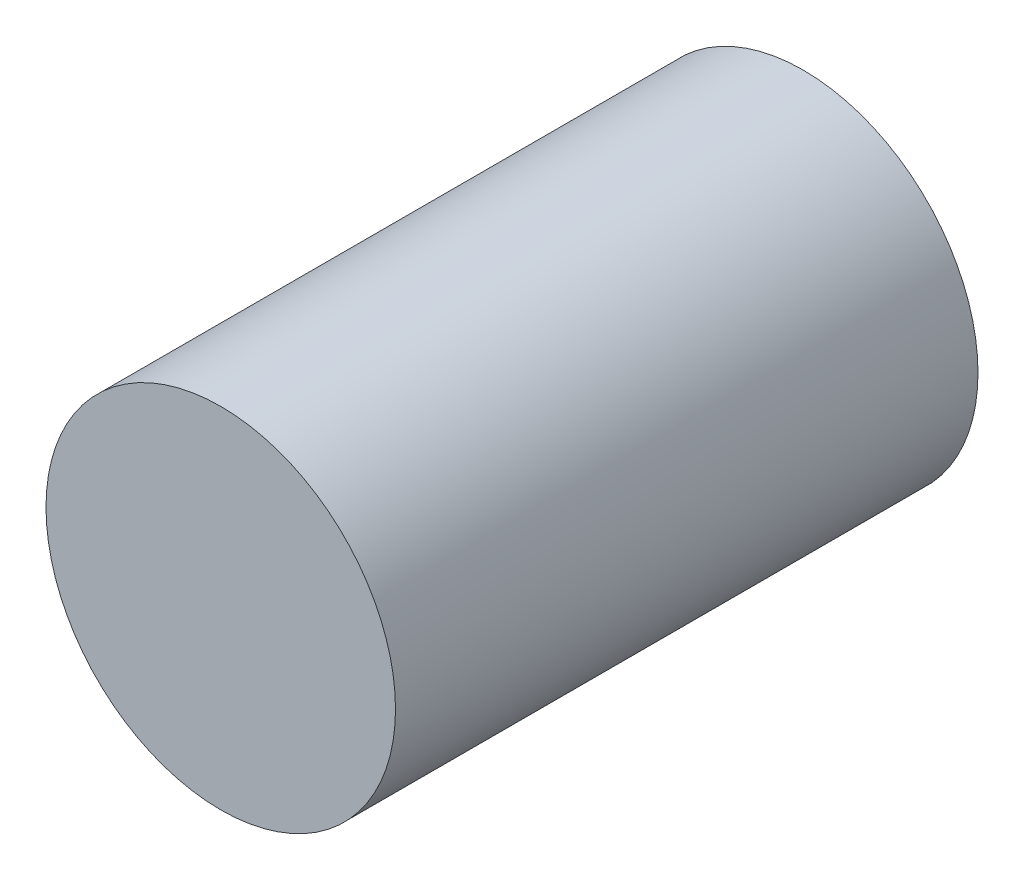
SolidWorks part; units mm, degrees
ref_plane "Front" through (0, 0, 0) normal (0, 0, 1) x (1, 0, 0)
ref_plane "Top" through (0, 0, 0) normal (0, 1, 0) x (1, 0, 0)
ref_plane "Right" through (0, 0, 0) normal (1, 0, 0) x (0, 0, -1)
sketch "Sketch1" plane through (0, 0, 0) normal (0, 0, 1) x (1, 0, 0)
  circle A0 centre (0, 0) radius 3
  dimension "D1" = 6
extrude "Boss-Extrude1" add sketch "Sketch1" along normal blind 10
ref_plane "Plane1" through (0, 0, 5) normal (0, 0, 1) x (1, 0, 0)
ref_axis "Axis1" through (0, -16.4559, 5) along (0, 1, 0)
